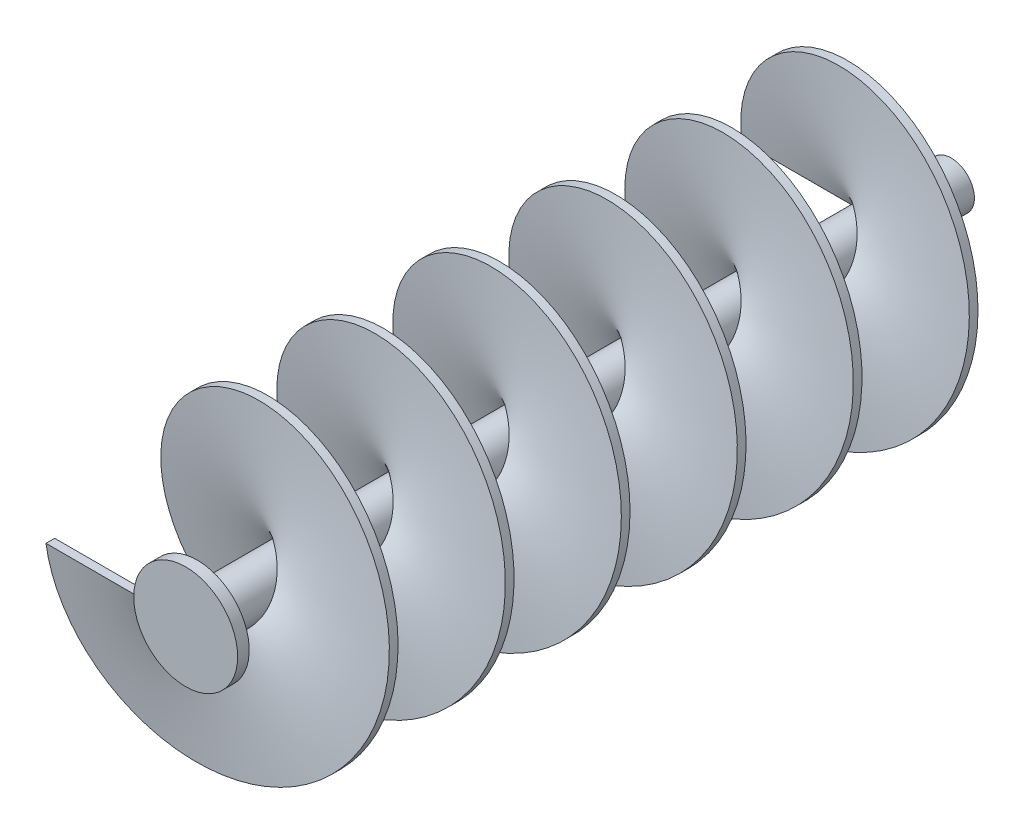
SolidWorks part; units mm, degrees
ref_plane "Front Plane" through (0, 0, 0) normal (0, 0, 1) x (1, 0, 0)
ref_plane "Top Plane" through (0, 0, 0) normal (0, 1, 0) x (1, 0, 0)
ref_plane "Right Plane" through (0, 0, 0) normal (1, 0, 0) x (0, 0, -1)
sketch "Sketch1" plane through (0, 0, 0) normal (0, 0, 1) x (1, 0, 0)
  circle A0 centre (0, 0) radius 4
  dimension "D1" = 8
extrude "Boss-Extrude1" add sketch "Sketch1" along normal blind 120
sketch "Sketch8" plane through (0, 0, 120) normal (0, 0, 1) x (1, 0, 0)
  circle A0 centre (0, 0) radius 4
extrude "Boss-Extrude2" add sketch "Sketch8" along normal blind 10
ref_plane "Plane3" through (0, 0, 10) normal (0, 0, 1) x (1, 0, 0)
sketch "Sketch16" plane through (0, 0, 10) normal (0, 0, 1) x (1, 0, 0)
  circle A0 centre (0, 0) radius 4
curve "Helix/Spiral3" pitch 20 height 120 radius 4 left hand yes centre (0, 0, 10) axis (0, 0, 1) start towards (-1, 0, 0)
ref_plane "Plane4" through (0, 0, 130) normal (0, 0, 1) x (1, 0, 0)
sketch "Sketch57" plane through (0, 0, 0) normal (0, 1, 0) x (1, 0, 0)
  line L0 (-3.9994, -11.5864) -> (-24.4994, -11.5864)
  line L1 (-3.9994, -11.5864) -> (-3.9994, -10.0864)
  line L2 (-24.4994, -11.5864) -> (-24.4994, -10.0864)
  line L3 (-3.9994, -10.0864) -> (-24.4994, -10.0864)
  dimension "D1" = 1.5
  dimension "D2" = 20.5
sweep "Sweep8" add profiles "Sketch57" path "Helix/Spiral3"
sketch "Sketch63" plane through (0, 0, 130) normal (0, 0, 1) x (1, 0, 0)
  circle A0 centre (0, 0) radius 8.9526
extrude "Boss-Extrude5" add sketch "Sketch63" along normal blind 2
